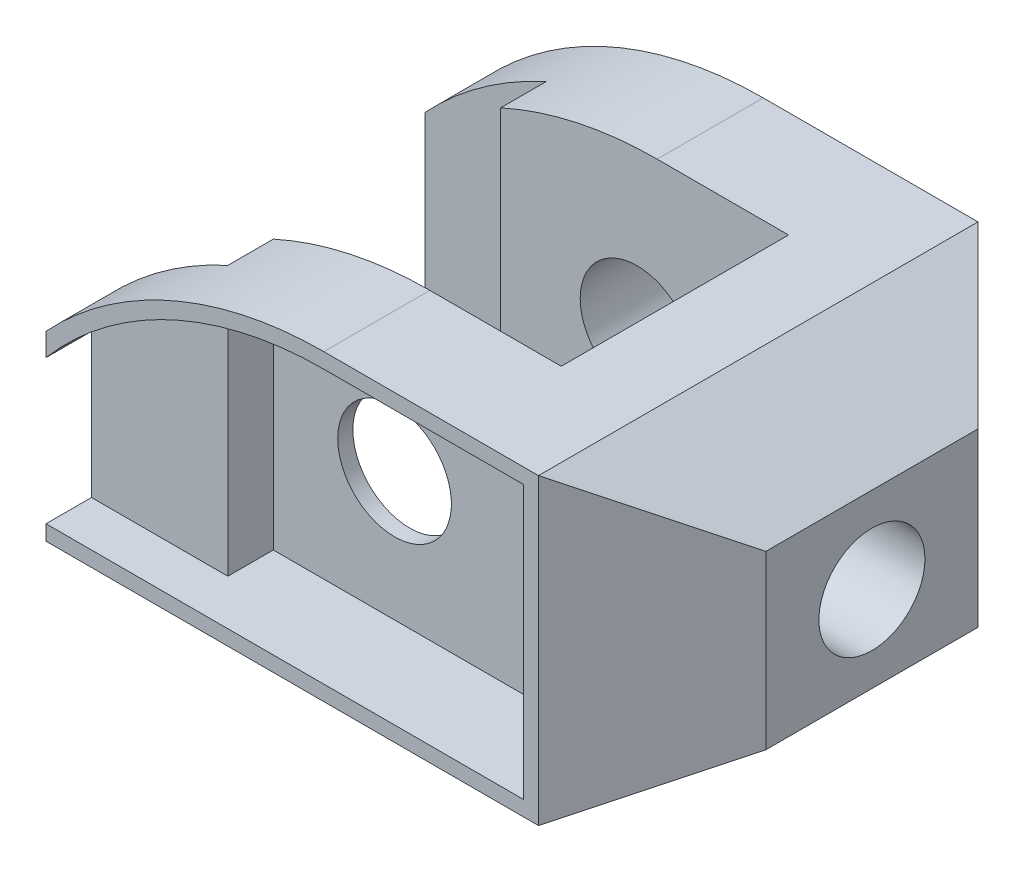
SolidWorks part; units mm, degrees
material "1060 Alloy"
ref_plane "Front Plane" through (0, 0, 0) normal (0, 0, 1) x (1, 0, 0)
ref_plane "Top Plane" through (0, 0, 0) normal (0, 1, 0) x (1, 0, 0)
ref_plane "Right Plane" through (0, 0, 0) normal (1, 0, 0) x (0, 0, -1)
sketch "Sketch1" plane through (0, 0, 0) normal (0, 0, 1) x (1, 0, 0)
  line L0 (-10.1776, 0) -> (8.7738, 0) construction
  line L1 (0, 9.7682) -> (0, -9.3002) construction
  line L2 (-34, -19) -> (31, -19)
  line L3 (31, -19) -> (46, -10.3397)
  line L4 (46, -10.3397) -> (46, 12.3397)
  line L5 (46, 12.3397) -> (31, 21)
  line L6 (31, 21) -> (2.6606, 21)
  line L7 (-34, -19) -> (-34, 5)
  circle A0 centre (0, 0) radius 7.5
  arc A1 (2.6606, 21) -> (-34, 5) centre (2.6606, -29) ccw
  dimension "D1" = 15
  dimension "D11" = 50
  dimension "D2" = 65
  dimension "D3" = 31
  dimension "D4" = 15
  dimension "D5" = 30
  dimension "D6" = 15
  dimension "D7" = 30
  dimension "D8" = 40
  dimension "D9" = 24
  dimension "D10" = 19
extrude "Boss-Extrude1" add sketch "Sketch1" along normal blind 58
sketch "Sketch2" plane through (0, -19, 0) normal (0, -1, 0) x (1, 0, 0)
  line L0 (-34, 50) -> (-18, 50)
  line L1 (-34, 58) -> (-34, 0) construction
  line L2 (-18, 50) -> (-18, 44)
  line L3 (-18, 44) -> (20, 44)
  line L4 (20, 44) -> (20, 14)
  line L5 (20, 14) -> (-18, 14)
  line L6 (-18, 14) -> (-18, 8)
  line L7 (-18, 8) -> (-34, 8)
  line L8 (-34, 8) -> (-34, 50)
  line L9 (-34, 58) -> (31, 58) construction
  line L10 (-34, 0) -> (31, 0) construction
  line L11 (31, 58) -> (31, 0) construction
  dimension "D1" = 8
  dimension "D2" = 8
  dimension "D3" = 11
  dimension "D4" = 6
  dimension "D5" = 6
  dimension "D6" = 16
  dimension "D7" = 16
extrude "Cut-Extrude1" cut sketch "Sketch2" against normal up to next
sketch "Sketch3" plane through (46, 0, 0) normal (1, 0, 0) x (0, 0, -1)
  line L0 (-58, -19) -> (0, -19) construction
  line L1 (-58, -10.3397) -> (-58, 12.3397) construction
  circle A0 centre (-29, 1) radius 7
  point P2 (0, 0)
  dimension "D1" = 14
  dimension "D2" = 20
  dimension "D3" = 29
extrude "Cut-Extrude2" cut sketch "Sketch3" against normal up to next
chamfer "Chamfer1" distance 15 angle 45 2 edges at (46, 1, 0) (46, 1, 58)
sketch "Sketch4" plane through (0, 0, 58) normal (0, 0, 1) x (1, 0, 0)
  line L3 (-34, 5) -> (-34, -19) construction
  line L4 (-34, 1.9839) -> (-34, -17)
  line L5 (-16, 15.2242) -> (-16, -17)
  line L6 (-34, -17) -> (29, -17)
  line L7 (29, -17) -> (29, 19)
  line L8 (29, 19) -> (2.6606, 19)
  line L9 (-34, -17) -> (29, -17)
  line L10 (29, -17) -> (29, 19)
  line L11 (29, 19) -> (2.6606, 19)
  arc A2 (2.6606, 19) -> (-32.5336, 3.64) centre (2.6606, -29) ccw
  arc A3 (2.6606, 19) -> (-34, 1.9839) centre (2.6606, -29) ccw
  point P5 (0, 0)
  point P6 (-16, 15.2242)
  point P8 (0, 0)
  point P9 (-16, -17)
  line M9 (-34, 5) -> (-34, -19)
  circle M10 centre (0, 0) radius 7.5
  dimension "D2" = 2
  dimension "D1" = 2
extrude "Cut-Extrude3" cut sketch "Sketch4" against normal blind 6 contours L5 A3 L9 M9 region at (-24.2689, -3.3823, 58)
extrude "Cut-Extrude4" cut sketch "Sketch4<3>" against normal blind 12 contours L11 A3 L5 L9 L10 M10 region at (7.5996, 0.8499, 58)
sketch "Sketch4<3>" plane through (0, 0, 58) normal (0, 0, 1) x (1, 0, 0) same geometry as "Sketch4"
equation "\"A\"= 58"
equation "\"B\"= 40"
equation "\"C\"= 65"
